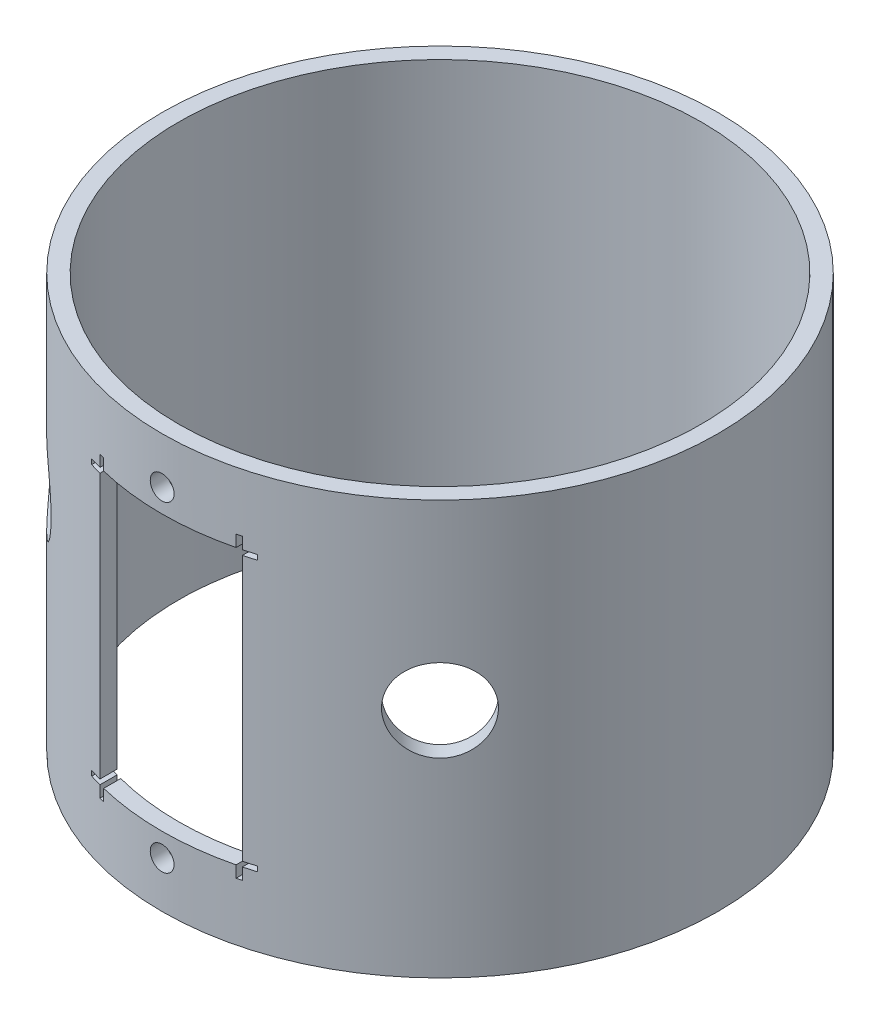
SolidWorks part; units mm, degrees
ref_plane "Front Plane" through (0, 0, 0) normal (0, 0, 1) x (1, 0, 0)
ref_plane "Top Plane" through (0, 0, 0) normal (0, 1, 0) x (1, 0, 0)
ref_plane "Right Plane" through (0, 0, 0) normal (1, 0, 0) x (0, 0, -1)
sketch "Sketch1" plane through (0, 0, 0) normal (0, 1, 0) x (1, 0, 0)
  circle A0 centre (0, 0) radius 42.672
extrude "Boss-Extrude1" add sketch "Sketch1" along normal blind 63.5
sketch "Sketch2" plane through (0, 0, 0) normal (0, 1, 0) x (1, 0, 0)
  circle A0 centre (0, 0) radius 40.132
extrude "Cut-Extrude1" cut sketch "Sketch2" along normal through all
ref_plane "Plane1" through (0, 31.75, 0) normal (0, 1, 0) x (1, 0, 0)
sketch "Sketch3" plane through (0, 0, 0) normal (0, 0, 1) x (1, 0, 0)
  line L0 (-12.7, 52.07) -> (-12.7, 52.832)
  line L1 (-10.16, 11.43) -> (10.16, 11.43)
  line L2 (-10.16, 11.43) -> (-10.16, 52.07)
  line L3 (-10.16, 52.07) -> (10.16, 52.07)
  line L4 (10.16, 11.43) -> (10.16, 52.07)
  line L5 (-12.7, 52.07) -> (12.7, 52.07)
  line L6 (0, 52.07) -> (0, 52.832)
  line L7 (-12.7, 52.832) -> (12.7, 52.832)
  line L8 (12.7, 52.07) -> (12.7, 52.832)
  line L9 (46.9392, 31.75) -> (-46.9392, 31.75) construction
  line L10 (12.7, 11.43) -> (12.7, 10.668)
  line L11 (-12.7, 11.43) -> (-12.7, 10.668)
  line L12 (-12.7, 11.43) -> (12.7, 11.43)
  line L13 (-12.7, 10.668) -> (12.7, 10.668)
  line L14 (10.16, 8.89) -> (10.922, 8.89)
  line L15 (10.16, 31.75) -> (10.922, 31.75)
  line L16 (10.16, 8.89) -> (10.16, 54.61)
  line L17 (10.16, 54.61) -> (10.922, 54.61)
  line L18 (10.922, 8.89) -> (10.922, 54.61)
  line L19 (0, -34.925) -> (0, 34.925) construction
  line L20 (-10.16, 8.89) -> (-10.922, 8.89)
  line L21 (-10.16, 54.61) -> (-10.922, 54.61)
  line L22 (-10.16, 8.89) -> (-10.16, 54.61)
  line L23 (-10.922, 8.89) -> (-10.922, 54.61)
  circle A0 centre (0, 56.388) radius 1.8288
  circle A1 centre (0, 7.112) radius 1.8288
  point P0 (0, 0)
  dimension "D1" = 20.32
  dimension "D2" = 40.64
  dimension "D5" = 0.762
  dimension "D6" = 22.86
extrude "Cut-Extrude2" cut sketch "Sketch3" along normal through all contours A0 | A1 | L1 L4 L5 L3 L2 | L22 L3 L6 L7 | L23 L5 L22 L7 | L23 L7 L22 L21 | L5 L23 L7 L0 | L23 L12 L2 L5 | L5 L16 L7 L6 | L7 L18 L17 L16 | L18 L5 L8 L7 | L5 L18 L7 L16 | L15 L18 L5 L4 | L12 L10 L13 L11 | L22 L21 L23 L20 | L18 L17 L16 L14 region at (-11.811, 52.451, 0) region at (-10.541, 52.451, 0) region at (-10.541, 31.75, 0) region at (-10.541, 53.721, 0) region at (0, 31.75, 0) region at (-5.08, 52.451, 0) region at (5.08, 52.451, 0) region at (10.541, 41.91, 0) region at (10.541, 52.451, 0) region at (10.541, 53.721, 0) region at (11.811, 52.451, 0) region at (0, 56.388, 0) region at (0, 7.112, 0)
ref_axis "Axis1" through (0, 66.675, 0) along (0, -1, 0)
ref_plane "Plane2" through (0, 0, 0) normal (-0.7071, 0, 0.7071) x (0, -1, 0)
ref_plane "Plane3" through (0, 0, 0) normal (-0.7071, 0, -0.7071) x (0, -1, 0)
sketch "Sketch4" plane through (0, 0, 0) normal (-0.7071, 0, 0.7071) x (0, -1, 0)
  circle A0 centre (-35.56, 0) radius 6.35
extrude "Cut-Extrude3" cut sketch "Sketch4" along normal through all
sketch "Sketch5" plane through (0, 0, 0) normal (-0.7071, 0, -0.7071) x (0, -1, 0)
  circle A0 centre (-35.56, 0) radius 6.35
extrude "Cut-Extrude4" cut sketch "Sketch5" against normal through all
